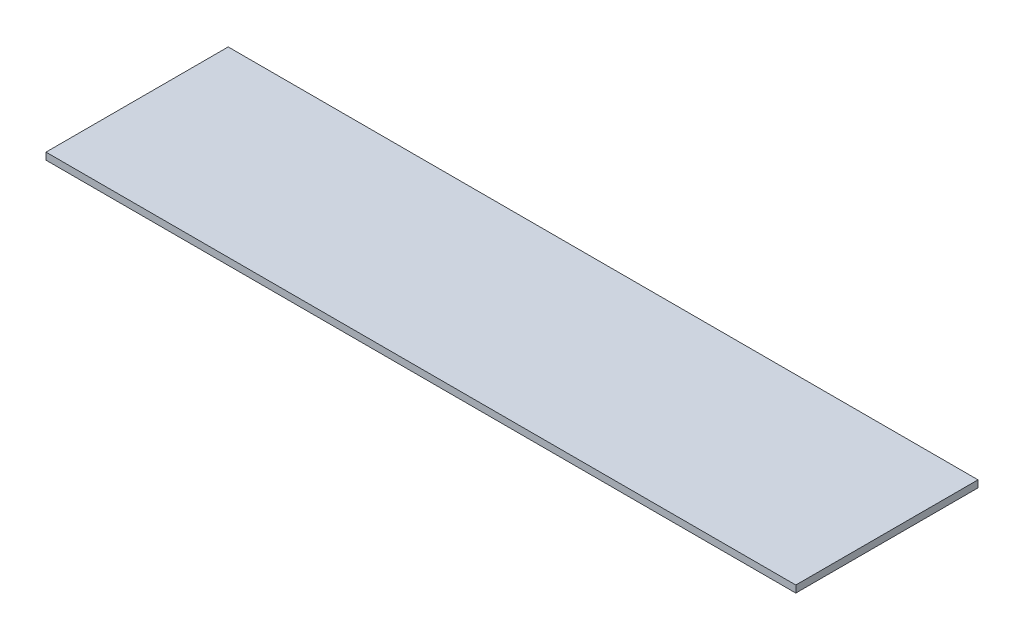
SolidWorks part; units mm, degrees
material "ABS"
ref_plane "Front Plane" through (0, 0, 0) normal (0, 0, 1) x (1, 0, 0)
ref_plane "Top Plane" through (0, 0, 0) normal (0, 1, 0) x (1, 0, 0)
ref_plane "Right Plane" through (0, 0, 0) normal (1, 0, 0) x (0, 0, -1)
sketch "Sketch1" plane through (0, 0, 0) normal (0, 1, 0) x (1, 0, 0)
  line L1 (0, 0) -> (2140, 0)
  line L2 (0, 0) -> (0, 520)
  line L3 (0, 520) -> (2140, 520)
  line L4 (2140, 0) -> (2140, 520)
  dimension "D1" = 520
  dimension "D2" = 2140
extrude "Boss-Extrude1" add sketch "Sketch1" along normal blind 20
